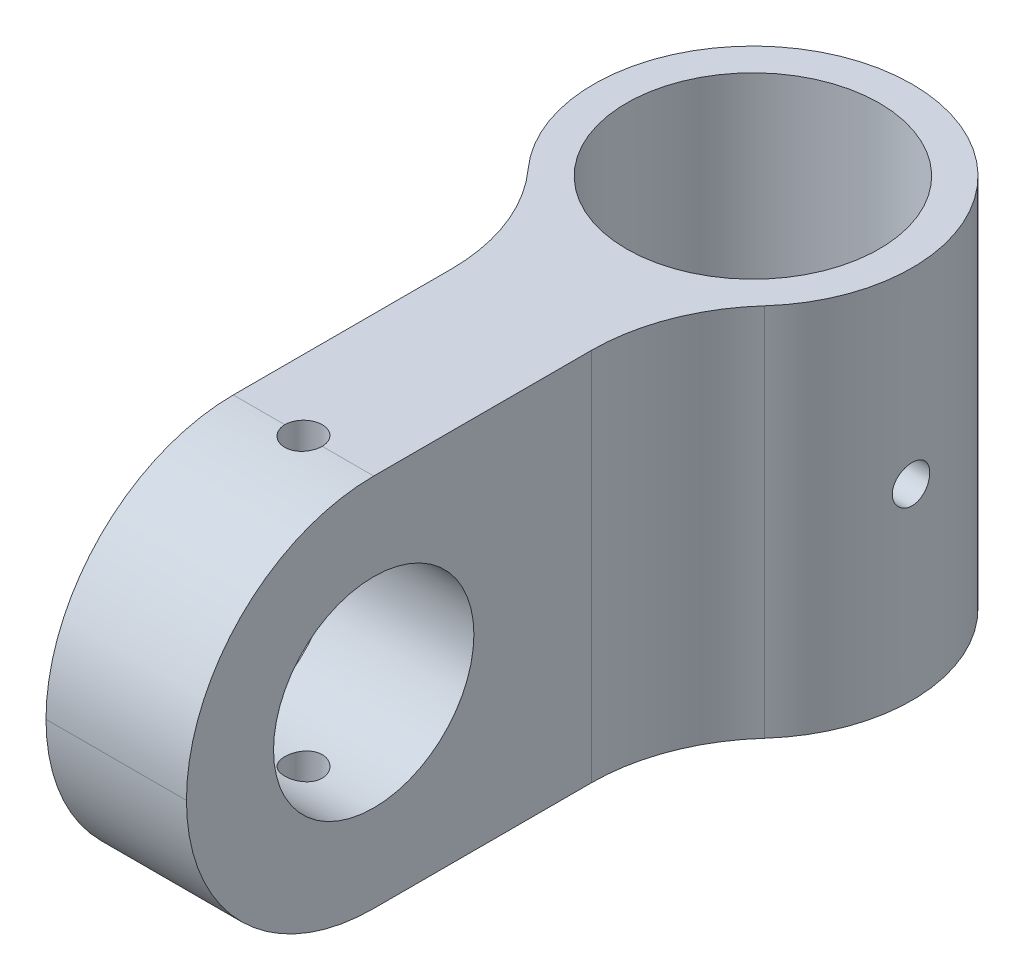
SolidWorks part; units mm, degrees
ref_plane "Front Plane" through (0, 0, 0) normal (0, 0, 1) x (1, 0, 0)
ref_plane "Top Plane" through (0, 0, 0) normal (0, 1, 0) x (1, 0, 0)
ref_plane "Right Plane" through (0, 0, 0) normal (1, 0, 0) x (0, 0, -1)
sketch "Sketch1" plane through (0, 0, 0) normal (0, 1, 0) x (1, 0, 0)
  line L0 (-23.749, 0) -> (23.749, 0) construction
  line L2 (-9.525, 66.9847) -> (-9.525, 0)
  line L3 (-9.525, 0) -> (9.525, 0)
  line L4 (9.525, 66.9847) -> (9.525, 0)
  line L5 (0, -27.94) -> (0, 27.94) construction
  arc A0 (9.525, 66.9847) -> (-9.525, 66.9847) centre (0, 86.36) ccw
  circle A1 centre (0, 86.36) radius 17.145
  circle A2 centre (0, 25.4) radius 2.54
  dimension "D3" = 25.4
  dimension "D4" = 21.59
  dimension "D5" = 34.29
  dimension "D1" = 86.36
  dimension "D2" = 9.525
  dimension "D6" = 19.05
extrude "Boss-Extrude1" add sketch "Sketch1" along normal mid plane 50.8
sketch "Sketch2" plane through (9.525, 0, 0) normal (1, 0, 0) x (0, 0, -1)
  line L0 (23.749, 0) -> (-23.749, 0) construction
  line L1 (0, 23.749) -> (0, -23.749) construction
  line L2 (86.36, 25.4) -> (86.36, -25.4) construction
  circle A0 centre (25.4, 0) radius 13.589
  circle A1 centre (86.36, 0) radius 2.54
  dimension "D1" = 25.4
  dimension "D2" = 0
  dimension "D3" = 27.178
extrude "Cut-Extrude1" cut sketch "Sketch2" against normal through all both and the other way through all
fillet "Fillet1" radius 25.4 2 edges at (0, -25.4, 0) (0, 25.4, 0)
fillet "Fillet2" radius 25.4 2 edges at (-9.525, 0, -66.9847) (9.525, 0, -66.9847)
